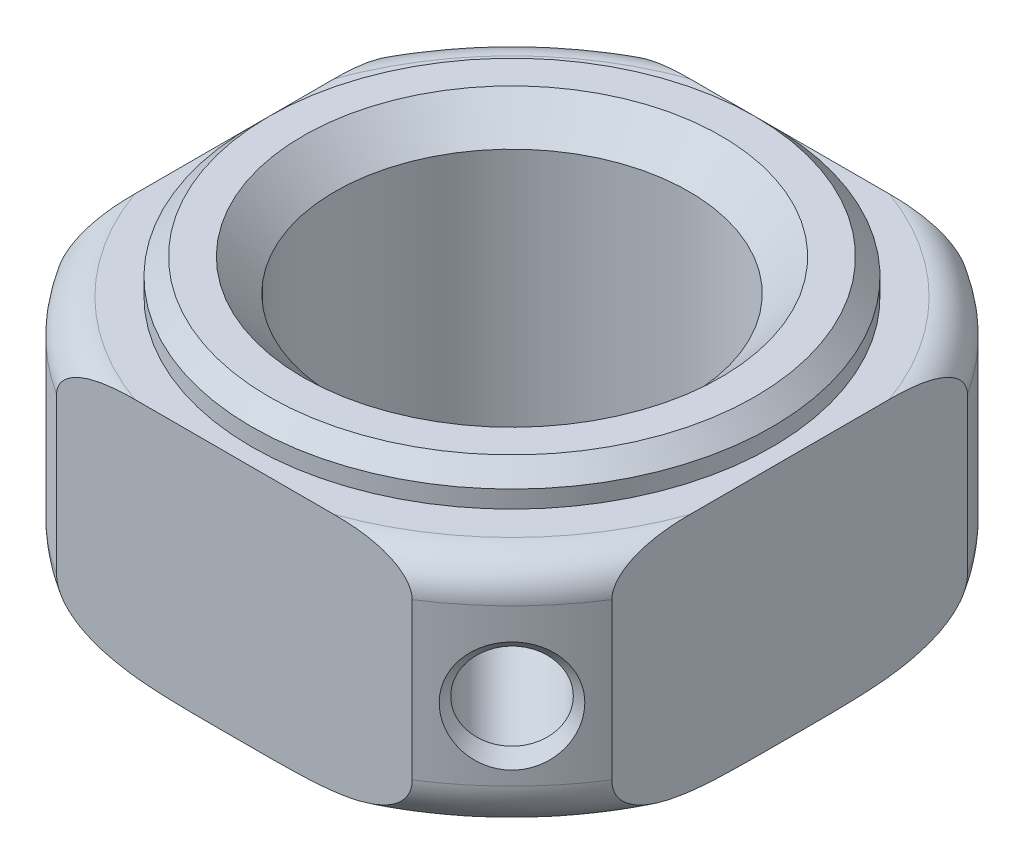
SolidWorks part; units mm, degrees
material "AISI 1020"
ref_plane "Plano frontal" through (0, 0, 0) normal (0, 0, 1) x (1, 0, 0)
ref_plane "Plano superior" through (0, 0, 0) normal (0, 1, 0) x (1, 0, 0)
ref_plane "Plano direito" through (0, 0, 0) normal (1, 0, 0) x (0, 0, -1)
sketch "Esboço1" plane through (0, 0, 0) normal (0, 1, 0) x (1, 0, 0)
  line L5 (5.1235, 8) -> (-5.1235, 8)
  line L6 (8, 5.1235) -> (8, -5.1235)
  line L7 (5.1235, -8) -> (-5.1235, -8)
  line L8 (-8, 5.1235) -> (-8, -5.1235)
  line L9 (0, -8) -> (0, 8) construction
  line L10 (8, 0) -> (-8, 0) construction
  arc A1 (-8, -5.1235) -> (-5.1235, -8) centre (0, 0) ccw
  arc A2 (5.1235, -8) -> (8, -5.1235) centre (0, 0) ccw
  arc A3 (8, 5.1235) -> (5.1235, 8) centre (0, 0) ccw
  arc A4 (-5.1235, 8) -> (-8, 5.1235) centre (0, 0) ccw
  point P0 (0, 0)
  dimension "D4" = 19
  dimension "D1" = 16
  dimension "D2" = 16
extrude "Ressalto-extrusão1" add sketch "Esboço1" along normal blind 7 contours A1 L7 A2 L6 A3 L5 A4 L8
sketch "Esboço2" plane through (0, 7, 0) normal (0, 1, 0) x (1, 0, 0)
  circle A0 centre (0, 0) radius 7.5
  dimension "D1" = 15
extrude "Ressalto-extrusão2" add sketch "Esboço2" along normal blind 1
hole_wizard "Furo roscado de M121" positions "Esboço3" profile "Esboço4" tap size "M12" standard "ISO" end condition through all
sketch "Esboço3" plane through (0, 8, 0) normal (0, 1, 0) x (1, 0, 0)
  point P0 (0, 0)
sketch "Esboço4" plane through (0, 8, 0) normal (1, 0, 0) x (0, 0, 1)
  line L0 (0, 0) -> (0, 8)
  line L1 (0, 8) -> (5.1, 8)
  line L2 (5.1, 8) -> (5.1, 0.925)
  line L3 (5.1, 0.925) -> (6.025, 0)
  line L5 (6.025, 0) -> (0, 0)
  line L6 (-5.1, 0.925) -> (-6.025, 0) construction
  line L11 (0, -6.35) -> (0, 107.95) construction
  dimension "Thru Tap Drill Dia." = 10.2
  dimension "Thru Tap Drill Depth" = 8
  dimension "Near C'Sink Dia." = 12.05
  dimension "Near C'Sink Angle" = 90
cosmetic thread "Rosca de furo6" parameters "D2"=12
fillet "Filete1" radius 1 4 edges at (-6.7175, 7, -6.7175) (6.7175, 7, -6.7175) (-6.7175, 7, 6.7175) (6.7175, 7, 6.7175)
fillet "Filete2" radius 1.5 4 edges at (6.7175, 0, -6.7175) (-6.7175, 0, -6.7175) (-6.7175, 0, 6.7175) (6.7175, 0, 6.7175)
chamfer "Chanfro1" distance 0.5 angle 45 1 edges at (0, 8, 7.5)
ref_plane "Plano1" through (6.7175, 0, 6.7175) normal (0.7071, 0, 0.7071) x (0, -1, 0)
hole_wizard "Furo roscado de M32" positions "Esboço5" profile "Esboço6" tap size "M3" standard "ISO" end condition up to next
sketch "Esboço5" plane through (6.7175, 0, 6.7175) normal (0.7071, 0, 0.7071) x (0, -1, 0)
  point P0 (-3.5, 0)
  dimension "D1" = 3.5
sketch "Esboço6" plane through (6.7175, 3.5, 6.7175) normal (0, 1, 0) x (0.7071, 0, -0.7071)
  line L0 (0, 0) -> (0, 4.4)
  line L1 (0, 4.4) -> (1.25, 4.4)
  line L2 (1.25, 4.4) -> (1.25, 0.35)
  line L3 (1.25, 0.35) -> (1.6, 0)
  line L5 (1.6, 0) -> (0, 0)
  line L6 (-1.25, 0.35) -> (-1.6, 0) construction
  line L11 (0, -6.35) -> (0, 107.95) construction
  dimension "Thru Tap Drill Dia." = 2.5
  dimension "Thru Tap Drill Depth" = 4.4
  dimension "Near C'Sink Dia." = 3.2
  dimension "Near C'Sink Angle" = 90
cosmetic thread "Rosca de furo5" parameters "D2"=3
